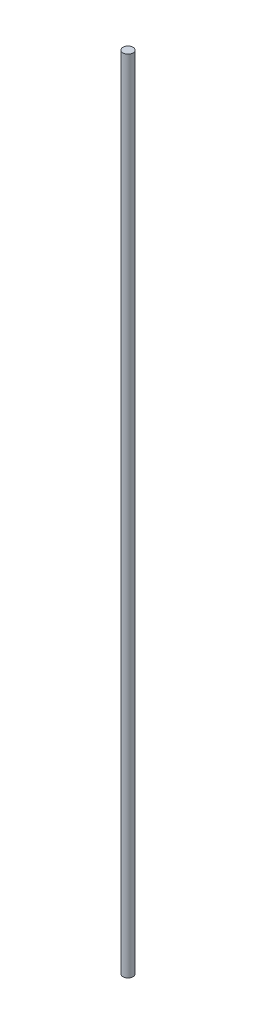
SolidWorks part; units mm, degrees
ref_plane "Front Plane" through (0, 0, 0) normal (0, 0, 1) x (1, 0, 0)
ref_plane "Top Plane" through (0, 0, 0) normal (0, 1, 0) x (1, 0, 0)
ref_plane "Right Plane" through (0, 0, 0) normal (1, 0, 0) x (0, 0, -1)
sketch "Sketch1" plane through (0, 0, 0) normal (0, 1, 0) x (1, 0, 0)
  circle A0 centre (0, 0) radius 3.175
  dimension "D1" = 6.35
extrude "Boss-Extrude1" add sketch "Sketch1" along normal mid plane 508
